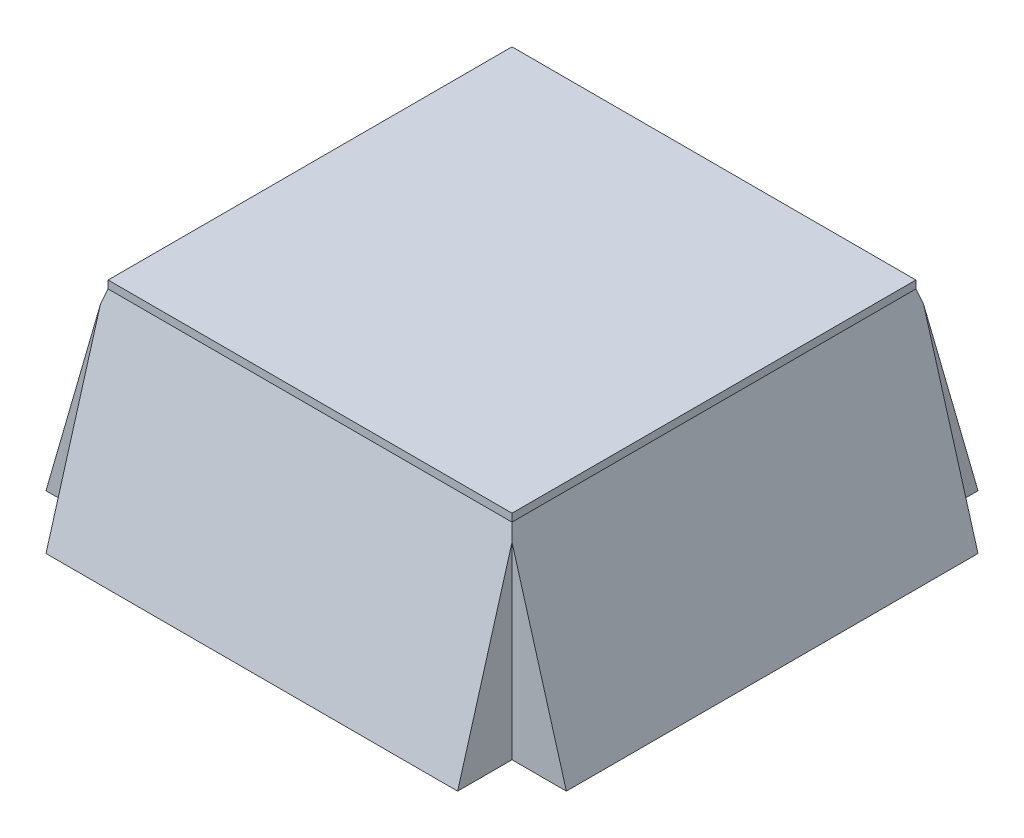
SolidWorks part; units mm, degrees
ref_plane "Alzado" through (0, 0, 0) normal (0, 0, 1) x (1, 0, 0)
ref_plane "Planta" through (0, 0, 0) normal (0, 1, 0) x (1, 0, 0)
ref_plane "Vista lateral" through (0, 0, 0) normal (1, 0, 0) x (0, 0, -1)
sketch "Croquis1" plane through (0, 0, 0) normal (0, 0, 1) x (1, 0, 0)
  line L0 (0, 0) -> (67, 0)
  line L1 (67, 0) -> (59.5, 26)
  line L2 (59.5, 26) -> (7.5, 26)
  line L3 (7.5, 26) -> (0, 0)
  dimension "D1" = 52
  dimension "D2" = 67
  dimension "D3" = 26
extrude "Saliente-Extruir1" add sketch "Croquis1" along normal blind 67
sketch "Croquis3" plane through (0, 0, 0) normal (1, 0, 0) x (0, 0, -1)
  line L0 (-67, 0) -> (-59.5, 26)
  line L1 (-67, 26) -> (0, 26) construction
  line L2 (0, 0) -> (-7.5, 26)
  line L3 (-59.5, 26) -> (-7.5, 26) construction
  line L4 (-67, 26) -> (-59.5, 26)
  line L5 (-7.5, 26) -> (0, 26)
  line L6 (0, 0) -> (0, 26) construction
  line L7 (-67, 0) -> (-67, 26) construction
  line L8 (0, 0) -> (0, 26)
  line L9 (-67, 0) -> (-67, 26)
  dimension "D1" = 52
extrude "Cortar-Extruir1" cut sketch "Croquis3" along normal blind 107
ref_plane "Plano2" through (33.5, 0, 0) normal (1, 0, 0) x (0, 0, -1)
sketch "Croquis5" plane through (0, 26, 0) normal (0, 1, 0) x (1, 0, 0)
  line L0 (7.5, -33.5) -> (59.5, -33.5) construction
  line L1 (33, -32.3544) -> (33, -8.5)
  line L2 (34, -32.3544) -> (34, -8.5)
  line L4 (7.5, -59.5) -> (7.5, -7.5) construction
  line L5 (7.5, -7.5) -> (59.5, -7.5) construction
  line L6 (59.5, -7.5) -> (59.5, -59.5) construction
  line L7 (59.5, -59.5) -> (7.5, -59.5) construction
  line L12 (8.5, -8.5) -> (33, -8.5)
  line L13 (58.5, -8.5) -> (58.5, -58.5)
  line L14 (58.5, -58.5) -> (8.5, -58.5)
  line L15 (8.5, -58.5) -> (8.5, -8.5)
  line L16 (34, -8.5) -> (58.5, -8.5)
  line L18 (8.5, -8.5) -> (58.5, -8.5) construction
  arc A0 (33, -32.3544) -> (34, -32.3544) centre (33.5, -33.5) ccw
  point P7 (0, 0)
  point P9 (32.9784, -6)
  point P12 (59.5, -33.5)
  point P13 (16.8158, -33.7393)
  point P14 (7.5, -33.5)
  point P15 (0, 0)
  point P16 (0, 0)
  dimension "D2" = 2.5
  dimension "D3" = 0.5
  dimension "D1" = 1
extrude "Cortar-Extruir2" cut sketch "Croquis5" against normal blind 107
sketch "Croquis6" plane through (33.5, 0, 0) normal (1, 0, 0) x (0, 0, -1)
  line L0 (-65.7115, 0) -> (-58.5, 25)
  line L1 (-67, 0) -> (0, 0) construction
  line L2 (-58.5, 0) -> (-58.5, 26) construction
  line L3 (-58.5, 25) -> (-8.5, 25)
  line L4 (-8.5, 0) -> (-8.5, 26) construction
  line L5 (-8.5, 25) -> (-1.2885, 0)
  line L6 (-1.2885, 0) -> (-65.7115, 0)
  line L7 (-33.5, 26) -> (-33.5, 0) construction
  line L8 (-59.5, 26) -> (-7.5, 26) construction
  line L9 (-7.5, 26) -> (0, 0) construction
  point P14 (0, 0)
  point P15 (-2.4257, 0)
  dimension "D1" = 1
extrude "Cortar-Extruir3" cut sketch "Croquis6" against normal blind 25 and the other way blind 25
ref_plane "Plano3" through (0, 0, 33.5) normal (0, 0, 1) x (1, 0, 0)
sketch "Croquis7" plane through (0, 0, 33.5) normal (0, 0, 1) x (1, 0, 0)
  line L0 (1.2885, 0) -> (8.5, 25)
  line L1 (0, 0) -> (67, 0) construction
  line L2 (8.5, 25) -> (58.5, 25)
  line L3 (58.5, 25) -> (65.7115, 0)
  line L4 (65.7115, 0) -> (1.2885, 0)
  line L5 (33.5, 0) -> (33.5, 26) construction
  line L6 (59.5, 26) -> (7.5, 26) construction
  line L7 (7.5, 26) -> (0, 0) construction
extrude "Cortar-Extruir4" cut sketch "Croquis7" against normal blind 25 and the other way blind 25
sketch "Croquis14" plane through (0, 0, 0) normal (0, -1, 0) x (1, 0, 0)
  line L0 (67, 0) -> (60, 0)
  line L1 (67, 67) -> (60, 67)
  line L2 (67, 67) -> (67, 60)
  line L3 (67, 60) -> (60, 60)
  line L4 (60, 67) -> (60, 60)
  line L5 (67, 0) -> (67, 7)
  line L6 (67, 7) -> (60, 7)
  line L7 (60, 0) -> (60, 7)
  line L8 (0, 0) -> (0, 7)
  line L9 (0, 0) -> (7, 0)
  line L10 (7, 0) -> (7, 7)
  line L11 (0, 7) -> (7, 7)
  line L12 (0, 67) -> (7, 67)
  line L13 (0, 67) -> (0, 60)
  line L14 (0, 60) -> (7, 60)
  line L15 (7, 67) -> (7, 60)
  dimension "D1" = 7
  dimension "D2" = 4
extrude "Cortar-Extruir6" cut sketch "Croquis14" against normal blind 70 contours L2 L1 L4 L3 | L12 L15 L14 L13 | L8 L11 L10 L9 | L0 L7 L6 L5
sketch "Croquis15" plane through (0, 26, 0) normal (0, 1, 0) x (1, 0, 0)
  line L0 (7.5, -59.5) -> (7.5, -7.5) construction
  line L1 (59.5, -59.5) -> (7.5, -59.5) construction
  line L2 (59.5, -59.5) -> (59.5, -7.5) construction
  line L3 (59.5, -7.5) -> (7.5, -7.5) construction
  line L4 (7.5, -59.5) -> (7.5, -7.5)
  line L5 (59.5, -59.5) -> (7.5, -59.5)
  line L6 (59.5, -59.5) -> (59.5, -7.5)
  line L7 (59.5, -7.5) -> (7.5, -7.5)
extrude "Saliente-Extruir10" add sketch "Croquis15" along normal blind 1
